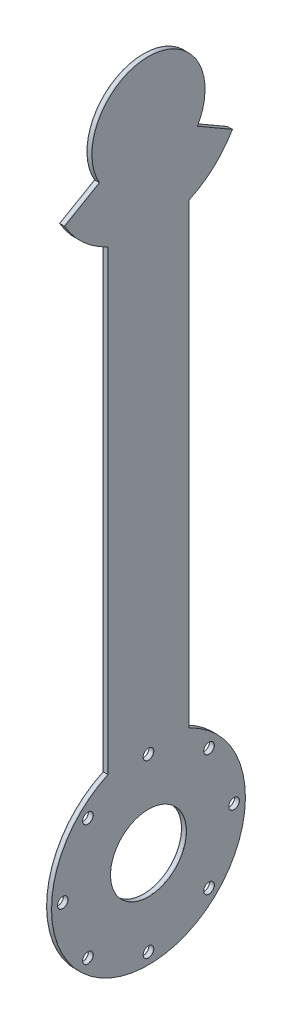
SolidWorks part; units mm, degrees
ref_plane "Front Plane" through (0, 0, 0) normal (0, 0, 1) x (1, 0, 0)
ref_plane "Top Plane" through (0, 0, 0) normal (0, 1, 0) x (1, 0, 0)
ref_plane "Right Plane" through (0, 0, 0) normal (1, 0, 0) x (0, 0, -1)
sketch "Sketch1" plane through (0, 0, 0) normal (1, 0, 0) x (0, 0, -1)
  line L0 (0, 0) -> (0, -392) construction
  line L1 (-30.3109, -17.5) -> (-51.9615, -30)
  line L2 (30.3109, -17.5) -> (51.9615, -30)
  line L3 (-20.3516, -196) -> (25.0726, -196) construction
  line L4 (-25, 0) -> (25, 0) construction
  line L5 (-25, -54.5436) -> (-25, -337.4564)
  line L6 (25, -54.5436) -> (25, -337.4564)
  arc A0 (-51.9615, -30) -> (51.9615, -30) centre (0, 0) ccw
  circle A1 centre (0, 0) radius 35
  circle A2 centre (0, -392) radius 60
  circle A3 centre (0, -392) radius 23.5
  point P15 (0, 0)
  dimension "D1" = 120
  dimension "D2" = 70
  dimension "D4" = 47
  dimension "D3" = 392
  dimension "D5" = 50
extrude "Boss-Extrude1" add sketch "Sketch1" against normal blind 0.25 and the other way blind 0.1 contours A1 | A1 L1 A0 L2 | A2 L6 A0 L5 | A2 A3 region at (0, -40.189, 0) region at (0, 0, 0) region at (0, -196, 0) region at (0, -333.6971, 0)
sketch "Sketch2" plane through (-0.25, 0, 0) normal (-1, 0, 0) x (0, 0, 1)
  line L4 (-30.3109, -17.5) -> (-51.9615, -30)
  line L5 (-25, -54.5436) -> (-25, -337.4564)
  line L6 (25, -337.4564) -> (25, -54.5436)
  line L7 (51.9615, -30) -> (30.3109, -17.5)
  line L8 (-30.3109, -17.5) -> (-51.9615, -30)
  line L9 (-25, -54.5436) -> (-25, -337.4564)
  line L10 (25, -337.4564) -> (25, -54.5436)
  line L11 (51.9615, -30) -> (30.3109, -17.5)
  circle A0 centre (0, -392) radius 23.5 construction
  circle A1 centre (0, -392) radius 23.5
  arc A4 (30.3109, -17.5) -> (-30.3109, -17.5) centre (0, 0) ccw
  arc A5 (-51.9615, -30) -> (-25, -54.5436) centre (0, 0) ccw
  arc A6 (-25, -337.4564) -> (25, -337.4564) centre (0, -392) ccw
  arc A7 (25, -54.5436) -> (51.9615, -30) centre (0, 0) ccw
  arc A8 (30.3109, -17.5) -> (-30.3109, -17.5) centre (0, 0) ccw
  arc A9 (-51.9615, -30) -> (-25, -54.5436) centre (0, 0) ccw
  arc A10 (-25, -337.4564) -> (25, -337.4564) centre (0, -392) ccw
  arc A11 (25, -54.5436) -> (51.9615, -30) centre (0, 0) ccw
  arc M9 (30.3109, -17.5) -> (-30.3109, -17.5) centre (0, 0) ccw
  line M10 (-30.3109, -17.5) -> (-51.9615, -30)
  arc M11 (-51.9615, -30) -> (-25, -54.5436) centre (0, 0) ccw
  line M12 (-25, -54.5436) -> (-25, -337.4564)
  arc M13 (-25, -337.4564) -> (25, -337.4564) centre (0, -392) ccw
  line M14 (25, -337.4564) -> (25, -54.5436)
  arc M15 (25, -54.5436) -> (51.9615, -30) centre (0, 0) ccw
  line M16 (51.9615, -30) -> (30.3109, -17.5)
  circle M17 centre (0, -392) radius 23.5
  dimension "D1" = 0
extrude "Boss-Extrude2" add sketch "Sketch2" along normal blind 2.5 separate body contours M16 M9 M10 M11 M12 M13 M14 M15 M17 region at (-0.25, -220.7516, 0)
sketch "Sketch4" plane through (-2.75, 0, 0) normal (-1, 0, 0) x (0, 0, 1)
  line L4 (51.9615, -30) -> (30.3109, -17.5)
  line L5 (-30.3109, -17.5) -> (-51.9615, -30)
  line L6 (-25, -54.5436) -> (-25, -337.4564)
  line L7 (25, -337.4564) -> (25, -54.5436)
  line L8 (51.9615, -30) -> (30.3109, -17.5)
  line L9 (-30.3109, -17.5) -> (-51.9615, -30)
  line L10 (-25, -54.5436) -> (-25, -337.4564)
  line L11 (25, -337.4564) -> (25, -54.5436)
  circle A0 centre (0, -392) radius 23.5 construction
  circle A1 centre (0, -392) radius 23.5
  arc A4 (30.3109, -17.5) -> (-30.3109, -17.5) centre (0, 0) ccw
  arc A5 (-51.9615, -30) -> (-25, -54.5436) centre (0, 0) ccw
  arc A6 (-25, -337.4564) -> (25, -337.4564) centre (0, -392) ccw
  arc A7 (25, -54.5436) -> (51.9615, -30) centre (0, 0) ccw
  arc A8 (30.3109, -17.5) -> (-30.3109, -17.5) centre (0, 0) ccw
  arc A9 (-51.9615, -30) -> (-25, -54.5436) centre (0, 0) ccw
  arc A10 (-25, -337.4564) -> (25, -337.4564) centre (0, -392) ccw
  arc A11 (25, -54.5436) -> (51.9615, -30) centre (0, 0) ccw
  dimension "D1" = 0
extrude "Boss-Extrude3" add sketch "Sketch4" along normal blind 0.25 separate body
sketch "Sketch5" plane through (0.1, 0, 0) normal (1, 0, 0) x (0, 0, -1)
  circle A0 centre (0, -392) radius 53
  point P3 (53, -392)
  point P4 (37.4767, -429.4767)
  point P7 (0, -445)
  point P8 (-37.4767, -429.4767)
  point P9 (-53, -392)
  point P10 (-37.4767, -354.5233)
  point P11 (0, -339)
  point P12 (37.4767, -354.5233)
  dimension "D1" = 106
  dimension "D2" = 8
hole_wizard "M6 Clearance Hole1" positions "Sketch5" profile "Sketch6" hole size "M6" standard "ISO" end condition through all
sketch "Sketch6" plane through (0.1, -354.5233, -37.4767) normal (0, 1, 0) x (0, 0, -1)
  line L0 (0, 0) -> (0, 3.1)
  line L1 (0, 3.1) -> (3.3, 3.1)
  line L2 (3.3, 3.1) -> (3.3, 0)
  line L5 (3.3, 0) -> (0, 0)
  line L11 (0, -6.35) -> (0, 107.95) construction
  dimension "Thru Hole Dia." = 6.6
  dimension "Thru Hole Depth" = 3.1
sketch "Sketch7" plane through (0.1, 0, 0) normal (1, 0, 0) x (0, 0, -1)
  circle A0 centre (0, 0) radius 17.5
  circle A1 centre (0, 0) radius 12
  point P4 (0, 12)
  point P7 (11.4127, 3.7082)
  point P8 (7.0534, -9.7082)
  point P9 (-7.0534, -9.7082)
  point P10 (-11.4127, 3.7082)
  dimension "D1" = 35
  dimension "D2" = 24
  dimension "D3" = 5
